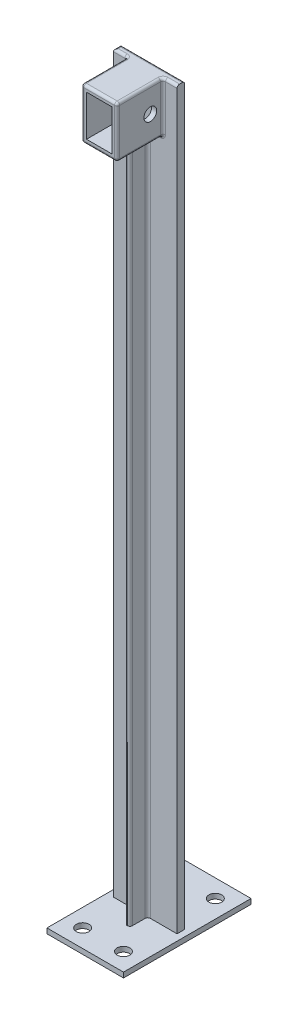
SolidWorks part; units mm, degrees
ref_plane "Front Plane" through (0, 0, 0) normal (0, 0, 1) x (1, 0, 0)
ref_plane "Top Plane" through (0, 0, 0) normal (0, 1, 0) x (1, 0, 0)
ref_plane "Right Plane" through (0, 0, 0) normal (1, 0, 0) x (0, 0, -1)
sketch "Sketch1" plane through (0, 0, 0) normal (0, 1, 0) x (1, 0, 0)
  line L1 (-12.5, 1.5) -> (12.5, 1.5)
  line L2 (-12.5, 1.5) -> (-12.5, -1.5)
  line L3 (-12.5, -1.5) -> (12.5, -1.5)
  line L4 (12.5, 1.5) -> (12.5, -1.5)
  line L5 (-12.5, 1.5) -> (12.5, -1.5) construction
  line L6 (-12.5, -1.5) -> (12.5, 1.5) construction
  point P0 (0, 0)
  dimension "D1" = 3
  dimension "D2" = 25
extrude "Boss-Extrude1" add sketch "Sketch1" along normal blind 288
sketch "Sketch2" plane through (0, 0, 1.5) normal (0, 0, 1) x (1, 0, 0)
  line L0 (-12.5, 288) -> (12.5, 288) construction
  line L1 (-7, 288) -> (7, 288)
  line L2 (-7, 288) -> (-7, 268)
  line L3 (-7, 268) -> (7, 268)
  line L4 (7, 288) -> (7, 268)
  line L5 (-7, 288) -> (7, 268) construction
  line L6 (-7, 268) -> (7, 288) construction
  line L8 (-5, 286) -> (5, 286)
  line L9 (-5, 286) -> (-5, 270)
  line L10 (-5, 270) -> (5, 270)
  line L11 (5, 286) -> (5, 270)
  line L12 (-5, 286) -> (5, 270) construction
  line L13 (-5, 270) -> (5, 286) construction
  point P0 (0, 278)
  point P7 (0, 278)
  dimension "D1" = 10
  dimension "D2" = 20
  dimension "D3" = 14
  dimension "D4" = 2
  dimension "D5" = 2
extrude "Boss-Extrude2" add sketch "Sketch2" along normal blind 18
sketch "Sketch3" plane through (-7, 0, 0) normal (-1, 0, 0) x (0, 0, 1)
  line L0 (1.5, 288) -> (1.5, 268) construction
  line L1 (19.5, 288) -> (1.5, 288) construction
  circle A0 centre (6.5, 278) radius 2.5
  point P6 (0, 0)
  dimension "D1" = 5
  dimension "D2" = 5
  dimension "D3" = 10
extrude "Cut-Extrude1" cut sketch "Sketch3" against normal through all both and the other way through all
sketch "Sketch4" plane through (0, 0, 0) normal (0, -1, 0) x (-1, 0, 0)
  line L1 (15, -25) -> (-15, -25)
  line L2 (15, -25) -> (15, 25)
  line L3 (15, 25) -> (-15, 25)
  line L4 (-15, -25) -> (-15, 25)
  line L5 (15, -25) -> (-15, 25) construction
  line L6 (15, 25) -> (-15, -25) construction
  point P0 (0, 0)
  dimension "D1" = 50
  dimension "D2" = 30
extrude "Boss-Extrude3" add sketch "Sketch4" along normal blind 2
sketch "Sketch5" plane through (0, 0, 1.5) normal (0, 0, 1) x (1, 0, 0)
  line L0 (0, 0) -> (1, 0)
  line L1 (-12.5, 0) -> (12.5, 0) construction
  line L2 (1, 0) -> (1, 268)
  line L3 (-7, 268) -> (7, 268) construction
  line L4 (1, 268) -> (0, 268)
  line L5 (0, 268) -> (-1, 268)
  line L6 (-1, 268) -> (-1, 0)
  line L7 (-1, 0) -> (0, 0)
  dimension "D1" = 1
  dimension "D2" = 1
extrude "Boss-Extrude4" add sketch "Sketch5" along normal blind 7
fillet "Fillet1" radius 1 22 edges at (-1, 268, 5) (-9.75, 288, 1.5) (-4, 268, 1.5) (4, 268, 1.5) (9.75, 288, 1.5) (0, 268, 19.5) (-7, 278, 19.5) (0, 288, 19.5) (7, 278, 19.5) (0, 288, -1.5) (-12.5, 288, 0) (1, 268, 5) (1, 134, 1.5) (1, 134, 8.5) (-1, 134, 8.5) (-1, 134, 1.5) (-7, 278, 1.5) (7, 278, 1.5) (7, 288, 10.5) (7, 268, 10.5) (-7, 268, 10.5) (-7, 288, 10.5)
sketch "Sketch6" plane through (0, 0, 0) normal (0, 1, 0) x (1, 0, 0)
  line L0 (-15, 25) -> (15, 25) construction
  line L1 (15, 25) -> (15, -25) construction
  line L2 (-15, -25) -> (-15, 25) construction
  line L3 (15, -25) -> (-15, -25) construction
  circle A0 centre (8, 18) radius 2.5
  circle A1 centre (-8, 18) radius 2.5
  circle A2 centre (-8, -18) radius 2.5
  circle A3 centre (8, -18) radius 2.5
  dimension "D1" = 7
  dimension "D3" = 7
  dimension "D5" = 7
  dimension "D2" = 7
  dimension "D4" = 7
extrude "Cut-Extrude2" cut sketch "Sketch6" against normal blind 10
